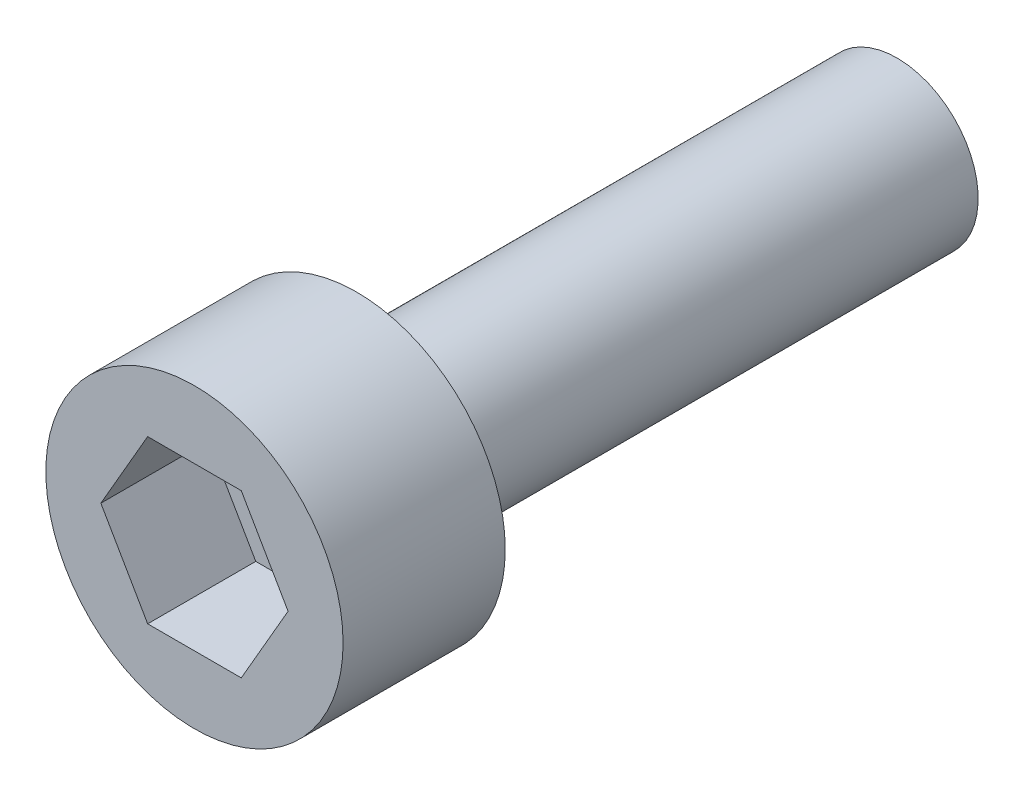
SolidWorks part; units mm, degrees
ref_plane "前视基准面" through (0, 0, 0) normal (0, 0, 1) x (1, 0, 0)
ref_plane "上视基准面" through (0, 0, 0) normal (0, 1, 0) x (1, 0, 0)
ref_plane "右视基准面" through (0, 0, 0) normal (1, 0, 0) x (0, 0, -1)
sketch "草图1" plane through (0, 0, 0) normal (0, 0, 1) x (1, 0, 0)
  line L1 (1.7321, 0) -> (0.866, 1.5)
  line L2 (0.866, 1.5) -> (-0.866, 1.5)
  line L3 (-0.866, 1.5) -> (-1.7321, 0)
  line L4 (-1.7321, 0) -> (-0.866, -1.5)
  line L5 (-0.866, -1.5) -> (0.866, -1.5)
  line L6 (0.866, -1.5) -> (1.7321, 0)
  circle A0 centre (0, 0) radius 2.75
  circle A1 centre (0, 0) radius 1.5 construction
  dimension "D1" = 5.5
  dimension "D2" = 3
extrude "凸台-拉伸1" add sketch "草图1" along normal blind 3
sketch "草图2" plane through (0, 0, 0) normal (0, 0, -1) x (-1, 0, 0)
  circle A0 centre (0, 0) radius 1.5
  dimension "D1" = 3
extrude "凸台-拉伸2" add sketch "草图2" along normal blind 10
cosmetic thread "装饰螺纹线1" parameters "D1"=10, "D2"=2
extrude "凸台-拉伸3" add sketch "草图1<3>" along normal blind 1 from surface contours L5 L6 L1 L2 L3 L4 region at (0, 0, 0) starting at face at (2.75, 0, 0)
sketch "草图1<3>" plane through (0, 0, 0) normal (0, 0, 1) x (1, 0, 0) same geometry as "草图1"
